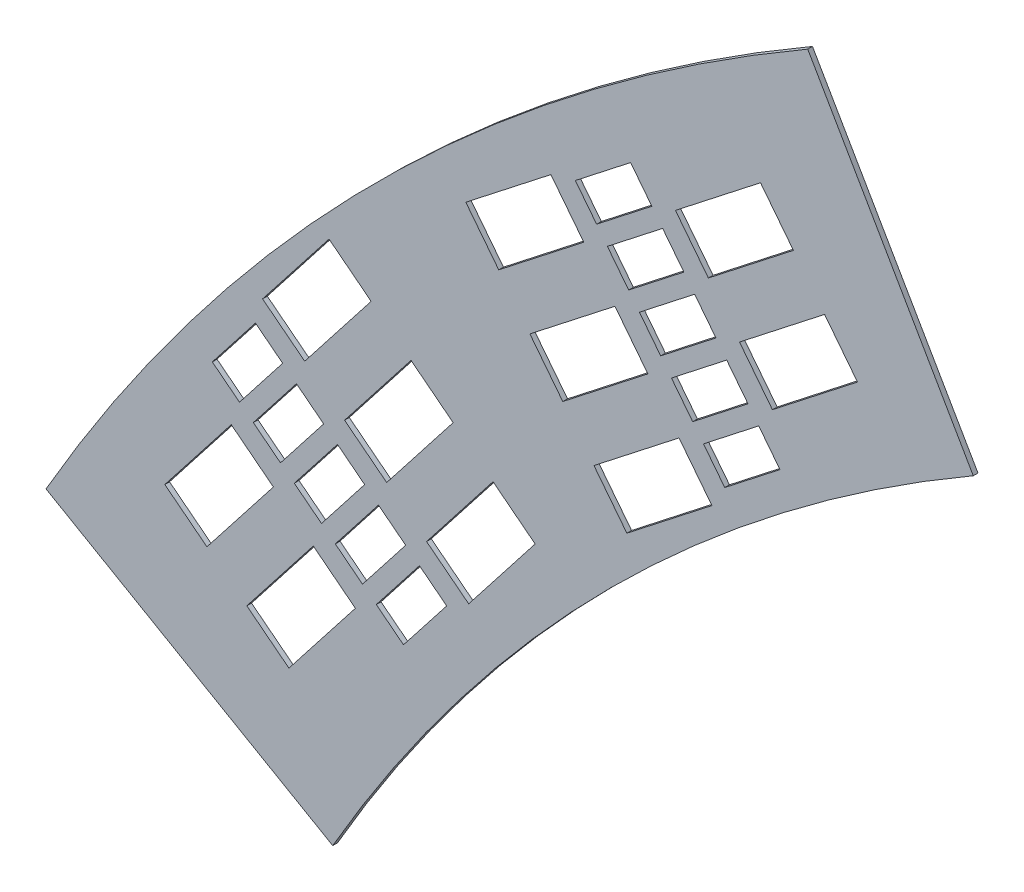
SolidWorks part; units mm, degrees
material "ABS"
ref_plane "Front Plane" through (0, 0, 0) normal (1, 0, 0) x (0, 1, 0)
ref_plane "Top Plane" through (0, 0, 0) normal (0, 0, 1) x (0, 1, 0)
ref_plane "Right Plane" through (0, 0, 0) normal (0, 1, 0) x (-1, 0, 0)
sketch "Sketch1" plane through (0, 0, 0) normal (0, 0, 1) x (0, 1, 0)
  line L0 (44, 76.2102) -> (37, 64.0859)
  line L1 (64.0859, 37) -> (76.2102, 44)
  line L2 (0, 0) -> (0, 88) construction
  line L3 (0, 0) -> (44, 76.2102) construction
  line L4 (0, 0) -> (88, 0) construction
  line L5 (0, 0) -> (76.2102, 44) construction
  arc A0 (76.2102, 44) -> (44, 76.2102) centre (0, 0) ccw
  arc A1 (64.0859, 37) -> (37, 64.0859) centre (0, 0) ccw
  arc A2 (37, 64.0859) -> (64.0859, 37) centre (0, 0) ccw construction
  arc A3 (44, 76.2102) -> (76.2102, 44) centre (0, 0) ccw construction
  dimension "D1" = 176
  dimension "D2" = 14
  dimension "D3" = 30
  dimension "D4" = 30
extrude "Boss-Extrude1" add sketch "Sketch1" along normal mid plane 0.2
sketch "Sketch2" plane through (0, 0, 0.1) normal (0, 0, 1) x (1, 0, 0)
  line L0 (0, 0) -> (-62.2254, 62.2254) construction
  line L1 (0, 0) -> (-54.1782, 69.3449) construction
  line L2 (0, 0) -> (-69.3449, 54.1782) construction
  line L3 (-47.2951, 60.1289) -> (-46.9011, 60.4367) construction
  line L4 (-47.2951, 60.1289) -> (-46.6794, 59.3409) construction
  line L5 (-46.9011, 60.4367) -> (-46.2854, 59.6487) construction
  line L6 (-46.6794, 59.3409) -> (-46.2854, 59.6487) construction
  line L7 (-47.2951, 60.1289) -> (-46.2854, 59.6487) construction
  line L8 (-46.9011, 60.4367) -> (-46.6794, 59.3409) construction
  line L25 (-48.2556, 62.1704) -> (-47.6399, 61.3824) construction
  line L26 (-61.3035, 47.5783) -> (-60.9957, 47.9723) construction
  line L27 (-61.3035, 47.5783) -> (-60.5155, 46.9627) construction
  line L28 (-60.9957, 47.9723) -> (-60.2077, 47.3567) construction
  line L29 (-60.5155, 46.9627) -> (-60.2077, 47.3567) construction
  line L30 (-61.3035, 47.5783) -> (-60.2077, 47.3567) construction
  line L31 (-60.9957, 47.9723) -> (-60.5155, 46.9627) construction
  line L32 (-48.6496, 61.8625) -> (-48.2556, 62.1704) construction
  line L33 (-48.6496, 61.8625) -> (-48.0339, 61.0745) construction
  line L34 (-48.0339, 61.0745) -> (-47.6399, 61.3824) construction
  line L35 (-49.61, 63.904) -> (-48.9943, 63.116) construction
  line L36 (-50.004, 63.5962) -> (-49.61, 63.904) construction
  line L37 (-50.004, 63.5962) -> (-49.3884, 62.8081) construction
  line L38 (-49.3884, 62.8081) -> (-48.9943, 63.116) construction
  line L39 (-50.9645, 65.6376) -> (-50.3488, 64.8496) construction
  line L40 (-51.3585, 65.3298) -> (-50.9645, 65.6376) construction
  line L41 (-51.3585, 65.3298) -> (-50.7428, 64.5418) construction
  line L42 (-50.7428, 64.5418) -> (-50.3488, 64.8496) construction
  line L43 (-52.3189, 67.3712) -> (-51.7033, 66.5832) construction
  line L44 (-52.7129, 67.0634) -> (-52.3189, 67.3712) construction
  line L45 (-52.7129, 67.0634) -> (-52.0973, 66.2754) construction
  line L46 (-52.0973, 66.2754) -> (-51.7033, 66.5832) construction
  line L47 (-46.7903, 59.8888) -> (-48.1447, 61.6224) construction
  line L48 (-62.2436, 46.7487) -> (-60.4182, 49.0852)
  line L49 (-62.2436, 46.7487) -> (-61.0931, 45.8498)
  line L50 (-60.4182, 49.0852) -> (-59.2677, 48.1863)
  line L51 (-61.0931, 45.8498) -> (-59.2677, 48.1863)
  line L56 (-62.2436, 46.7487) -> (-59.2677, 48.1863) construction
  line L57 (-60.4182, 49.0852) -> (-61.0931, 45.8498) construction
  line L58 (-63.9772, 48.1032) -> (-62.1518, 50.4396)
  line L59 (-63.9772, 48.1032) -> (-62.8267, 47.2043)
  line L64 (-62.8267, 47.2043) -> (-61.0013, 49.5407)
  line L65 (-62.1518, 50.4396) -> (-61.0013, 49.5407)
  line L66 (-62.7293, 49.3268) -> (-61.9413, 48.7111) construction
  line L67 (-63.0372, 48.9328) -> (-62.7293, 49.3268) construction
  line L72 (-63.0372, 48.9328) -> (-62.2492, 48.3171) construction
  line L73 (-62.2492, 48.3171) -> (-61.9413, 48.7111) construction
  line L74 (-65.7108, 49.4576) -> (-63.8854, 51.7941)
  line L75 (-65.7108, 49.4576) -> (-64.5603, 48.5588)
  line L80 (-64.5603, 48.5588) -> (-62.7349, 50.8952)
  line L81 (-63.8854, 51.7941) -> (-62.7349, 50.8952)
  line L82 (-64.463, 50.6812) -> (-63.675, 50.0656) construction
  line L83 (-64.7708, 50.2872) -> (-64.463, 50.6812) construction
  line L84 (-64.7708, 50.2872) -> (-63.9828, 49.6716) construction
  line L85 (-47.5091, 58.4009) -> (-45.1726, 60.2263)
  line L86 (-47.5091, 58.4009) -> (-48.4079, 59.5513)
  line L87 (-45.1726, 60.2263) -> (-46.0715, 61.3768)
  line L88 (-48.4079, 59.5513) -> (-46.0715, 61.3768)
  line L89 (-47.5091, 58.4009) -> (-46.0715, 61.3768) construction
  line L90 (-45.1726, 60.2263) -> (-48.4079, 59.5513) construction
  line L91 (-49.7624, 61.285) -> (-47.4259, 63.1104)
  line L92 (-48.8635, 60.1345) -> (-49.7624, 61.285)
  line L93 (-48.8635, 60.1345) -> (-46.5271, 61.9599)
  line L94 (-46.5271, 61.9599) -> (-47.4259, 63.1104)
  line L95 (-51.1168, 63.0186) -> (-48.7804, 64.844)
  line L96 (-50.218, 61.8681) -> (-51.1168, 63.0186)
  line L97 (-50.218, 61.8681) -> (-47.8815, 63.6935)
  line L98 (-47.8815, 63.6935) -> (-48.7804, 64.844)
  line L99 (-52.4713, 64.7522) -> (-50.1348, 66.5777)
  line L100 (-51.5724, 63.6017) -> (-52.4713, 64.7522)
  line L101 (-51.5724, 63.6017) -> (-49.236, 65.4272)
  line L102 (-49.236, 65.4272) -> (-50.1348, 66.5777)
  line L103 (-53.8258, 66.4858) -> (-51.4893, 68.3113)
  line L104 (-52.9269, 65.3353) -> (-53.8258, 66.4858)
  line L105 (-52.9269, 65.3353) -> (-50.5904, 67.1608)
  line L106 (-50.5904, 67.1608) -> (-51.4893, 68.3113)
  line L107 (-63.9828, 49.6716) -> (-63.675, 50.0656) construction
  line L108 (-67.4445, 50.8121) -> (-65.619, 53.1485)
  line L109 (-67.4445, 50.8121) -> (-66.294, 49.9132)
  line L110 (-66.294, 49.9132) -> (-64.4685, 52.2497)
  line L111 (-65.619, 53.1485) -> (-64.4685, 52.2497)
  line L112 (-66.1966, 52.0357) -> (-65.4086, 51.42) construction
  line L113 (-66.5044, 51.6417) -> (-66.1966, 52.0357) construction
  line L114 (-66.5044, 51.6417) -> (-65.7164, 51.026) construction
  line L115 (-65.7164, 51.026) -> (-65.4086, 51.42) construction
  line L116 (-69.1781, 52.1665) -> (-67.3527, 54.503)
  line L117 (-69.1781, 52.1665) -> (-68.0276, 51.2677)
  line L118 (-68.0276, 51.2677) -> (-66.2022, 53.6041)
  line L119 (-67.3527, 54.503) -> (-66.2022, 53.6041)
  line L120 (-67.9302, 53.3902) -> (-67.1422, 52.7745) construction
  line L121 (-68.238, 52.9961) -> (-67.9302, 53.3902) construction
  line L122 (-68.238, 52.9961) -> (-67.45, 52.3805) construction
  line L123 (-67.45, 52.3805) -> (-67.1422, 52.7745) construction
  line L124 (-60.7556, 47.4675) -> (-62.4893, 48.822) construction
  line L125 (-60.1177, 50.1194) -> (-57.3072, 53.7167)
  line L126 (-60.1177, 50.1194) -> (-58.3368, 48.728)
  line L127 (-57.3072, 53.7167) -> (-55.5263, 52.3253)
  line L128 (-58.3368, 48.728) -> (-55.5263, 52.3253)
  line L129 (-60.1177, 50.1194) -> (-55.5263, 52.3253) construction
  line L130 (-57.3072, 53.7167) -> (-58.3368, 48.728) construction
  line L131 (-60.7556, 47.4675) -> (-57.822, 51.2224) construction
  line L132 (-63.5849, 52.8283) -> (-60.7745, 56.4256)
  line L133 (-63.5849, 52.8283) -> (-61.804, 51.4369)
  line L134 (-61.804, 51.4369) -> (-58.9936, 55.0342)
  line L135 (-60.7745, 56.4256) -> (-58.9936, 55.0342)
  line L136 (-67.0522, 55.5373) -> (-64.2417, 59.1345)
  line L137 (-67.0522, 55.5373) -> (-65.2713, 54.1459)
  line L138 (-65.2713, 54.1459) -> (-62.4608, 57.7431)
  line L139 (-64.2417, 59.1345) -> (-62.4608, 57.7431)
  line L140 (-60.1177, 50.1194) -> (-63.5849, 52.8283) construction
  line L141 (-67.7186, 43.9641) -> (-64.9081, 47.5614)
  line L142 (-67.7186, 43.9641) -> (-65.9377, 42.5728)
  line L143 (-64.9081, 47.5614) -> (-63.1272, 46.17)
  line L144 (-65.9377, 42.5728) -> (-63.1272, 46.17)
  line L145 (-67.7186, 43.9641) -> (-63.1272, 46.17) construction
  line L146 (-64.9081, 47.5614) -> (-65.9377, 42.5728) construction
  line L147 (-62.4893, 48.822) -> (-65.4229, 45.0671) construction
  line L148 (-71.1858, 46.6731) -> (-68.3753, 50.2703)
  line L149 (-71.1858, 46.6731) -> (-69.4049, 45.2817)
  line L150 (-69.4049, 45.2817) -> (-66.5944, 48.8789)
  line L151 (-68.3753, 50.2703) -> (-66.5944, 48.8789)
  line L152 (-67.7186, 43.9641) -> (-71.1858, 46.6731) construction
  line L153 (-49.4422, 59.2509) -> (-53.0395, 56.4404)
  line L154 (-49.4422, 59.2509) -> (-48.0508, 57.47)
  line L155 (-53.0395, 56.4404) -> (-51.6481, 54.6595)
  line L156 (-48.0508, 57.47) -> (-51.6481, 54.6595)
  line L157 (-49.4422, 59.2509) -> (-51.6481, 54.6595) construction
  line L158 (-53.0395, 56.4404) -> (-48.0508, 57.47) construction
  line L159 (-50.5451, 56.9552) -> (-46.7903, 59.8888) construction
  line L160 (-52.1511, 62.7181) -> (-55.7484, 59.9076)
  line L161 (-52.1511, 62.7181) -> (-50.7597, 60.9372)
  line L162 (-50.7597, 60.9372) -> (-54.357, 58.1267)
  line L163 (-55.7484, 59.9076) -> (-54.357, 58.1267)
  line L164 (-54.86, 66.1854) -> (-58.4573, 63.3749)
  line L165 (-54.86, 66.1854) -> (-53.4686, 64.4045)
  line L166 (-53.4686, 64.4045) -> (-57.0659, 61.594)
  line L167 (-58.4573, 63.3749) -> (-57.0659, 61.594)
  line L168 (-49.4422, 59.2509) -> (-52.1511, 62.7181) construction
  line L169 (-45.4928, 62.2604) -> (-41.8955, 65.0709)
  line L170 (-45.4928, 62.2604) -> (-46.8842, 64.0413)
  line L171 (-41.8955, 65.0709) -> (-43.2869, 66.8518)
  line L172 (-46.8842, 64.0413) -> (-43.2869, 66.8518)
  line L173 (-45.4928, 62.2604) -> (-43.2869, 66.8518) construction
  line L174 (-41.8955, 65.0709) -> (-46.8842, 64.0413) construction
  line L175 (-48.1447, 61.6224) -> (-44.3899, 64.5561) construction
  line L176 (-48.2017, 65.7276) -> (-44.6044, 68.5381)
  line L177 (-48.2017, 65.7276) -> (-49.5931, 67.5085)
  line L178 (-49.5931, 67.5085) -> (-45.9958, 70.319)
  line L179 (-44.6044, 68.5381) -> (-45.9958, 70.319)
  line L180 (-45.4928, 62.2604) -> (-48.2017, 65.7276) construction
  arc A0 (-44, 76.2102) -> (-76.2102, 44) centre (0, 0) ccw construction
  circle A2 centre (0, 0) radius 75.5 construction
  point P9 (-46.7903, 59.8888)
  point P16 (-59.4948, 46.4824)
  point P18 (-60.7556, 47.4675)
  point P19 (-48.1447, 61.6224)
  point P24 (-49.4992, 63.3561)
  point P29 (-50.8536, 65.0897)
  point P34 (-52.2081, 66.8233)
  point P36 (-60.7556, 47.4675)
  point P37 (-57.822, 51.2224)
  point P42 (-62.4893, 48.822)
  point P68 (-64.2229, 50.1764)
  point P81 (-65.9565, 51.5309)
  point P94 (-67.6901, 52.8853)
  point P125 (-65.4229, 45.0671)
  point P152 (-50.5451, 56.9552)
  point P166 (-44.3899, 64.5561)
  dimension "D2" = 7
  dimension "D3" = 0.5
  dimension "D6" = 2.2
  dimension "D11" = 1.46
  dimension "D12" = 2.965
  dimension "D7" = 1
  dimension "D8" = 0.5
  dimension "D9" = 1.1
  dimension "D10" = 1.46
  dimension "D13" = 2.965
  dimension "D14" = 2.2
  dimension "D15" = 4.565
  dimension "D16" = 2.26
  dimension "D18" = 1
  dimension "D19" = 4.4
  dimension "D21" = 2.26
  dimension "D22" = 4.565
  dimension "D23" = 1
  dimension "D24" = 4.4
  dimension "D25" = 1
  dimension "D26" = 2.26
  dimension "D27" = 4.565
  dimension "D28" = 12.5
  dimension "D29" = 4.4
  dimension "D30" = 1
  dimension "D31" = 2.26
  dimension "D32" = 4.565
  dimension "D33" = 4.4
  dimension "D5" = 5
  dimension "D17" = 5
  dimension "D20" = 3
  dimension "D34" = 2
  dimension "D35" = 3
  dimension "D36" = 2
extrude "Cut-Extrude1" cut sketch "Sketch2" against normal through all
equation "\"D6@Sketch2\"=2 * \"D9@Sketch2\""
equation "\"D14@Sketch2\"=2 * \"D9@Sketch2\""
equation "\"D19@Sketch2\"=2 * \"D14@Sketch2\""
equation "\"D23@Sketch2\"=\"D18@Sketch2\""
equation "\"D24@Sketch2\"=\"D19@Sketch2\""
equation "\"D29@Sketch2\"=2 * \"D6@Sketch2\""
equation "\"D30@Sketch2\"=\"D25@Sketch2\""
equation "\"D33@Sketch2\"=\"D29@Sketch2\""
equation "\"D4@Sketch1\"=\"D3@Sketch1\""
equation "\"D1@Sketch2\"=\"D2@Sketch2\""
